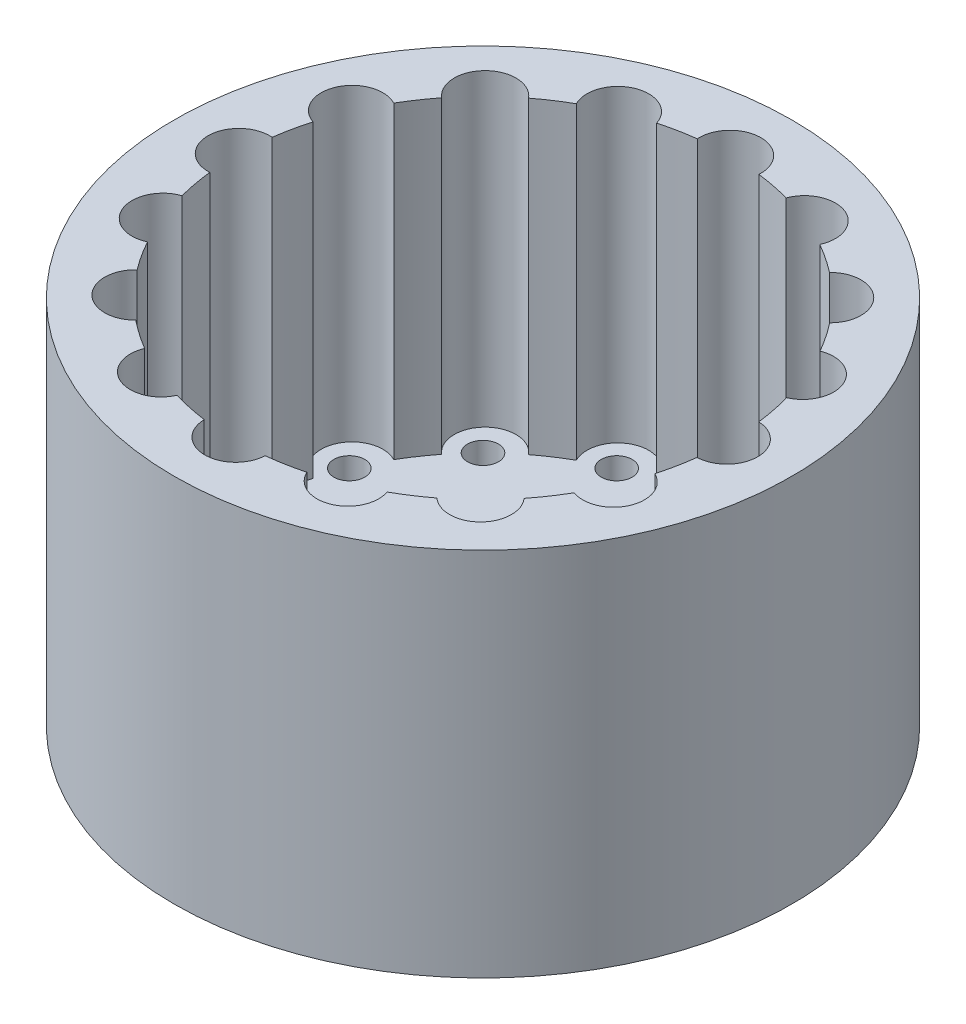
SolidWorks part; units mm, degrees
ref_plane "Front Plane" through (0, 0, 0) normal (0, 0, 1) x (1, 0, 0)
ref_plane "Top Plane" through (0, 0, 0) normal (0, 1, 0) x (1, 0, 0)
ref_plane "Right Plane" through (0, 0, 0) normal (1, 0, 0) x (0, 0, -1)
sketch "Sketch1" plane through (0, 0, 0) normal (0, 1, 0) x (1, 0, 0)
  arc A0 (-38.4721, 10.9498) -> (-39.6225, 5.4827) centre (0, 0) ccw
  arc A1 (4.9902, 39.6875) -> (-4.9902, 39.6875) centre (0, 40) ccw
  arc A2 (19.7423, 34.7885) -> (10.5038, 38.5963) centre (15.1971, 36.8722) ccw
  arc A3 (31.5425, 24.5981) -> (24.4561, 31.6528) centre (28.0405, 28.1668) ccw
  arc A4 (38.5639, 10.6218) -> (34.7247, 19.8543) centre (36.5748, 15.2091) ccw
  arc A5 (39.6831, -5.0248) -> (39.6903, 4.9683) centre (39.5008, -0.0281) ccw
  arc A6 (34.6812, -19.9303) -> (38.5373, -10.718) centre (36.373, -15.2253) ccw
  arc A7 (24.305, -31.769) -> (31.416, -24.7596) centre (27.6676, -28.0686) ccw
  arc A8 (10.1649, -38.6869) -> (19.4331, -34.9622) centre (14.7099, -36.6029) ccw
  arc A9 (-5.5266, -39.6164) -> (4.4678, -39.7497) centre (-0.5273, -39.5289) ccw
  arc A10 (-20.3279, -34.4496) -> (-11.148, -38.4151) centre (-15.7245, -36.4011) ccw
  arc A11 (-31.9737, -24.0351) -> (-25.0145, -31.2134) centre (-28.5678, -27.6957) ccw
  arc A12 (-38.7274, -10.0096) -> (-35.0397, -19.2929) centre (-37.1021, -14.7381) ccw
  arc A13 (-39.6225, 5.4827) -> (-39.7469, -4.4929) centre (-40.0281, 0.4992) ccw
  arc A14 (-34.5711, 20.1207) -> (-38.4721, 10.9498) centre (-36.9003, 15.6963) ccw
  arc A15 (-24.3492, 31.7351) -> (-31.4368, 24.7331) centre (-28.1949, 28.5397) ccw
  arc A16 (-10.477, 38.6035) -> (-19.6974, 34.814) centre (-15.2373, 37.074) ccw
  circle A17 centre (0, 0) radius 50
  arc A18 (-31.4368, 24.7331) -> (-34.5711, 20.1207) centre (0, 0) ccw
  arc A19 (-19.6974, 34.814) -> (-24.3492, 31.7351) centre (0, 0) ccw
  arc A20 (-4.9902, 39.6875) -> (-10.477, 38.6035) centre (0, 0) ccw
  arc A21 (10.5038, 38.5963) -> (4.9902, 39.6875) centre (0, 0) ccw
  arc A22 (24.4561, 31.6528) -> (19.7423, 34.7885) centre (0, 0) ccw
  arc A23 (34.7247, 19.8543) -> (31.5425, 24.5981) centre (0, 0) ccw
  arc A24 (39.6903, 4.9683) -> (38.5639, 10.6218) centre (0, 0) ccw
  arc A25 (38.5373, -10.718) -> (39.6831, -5.0248) centre (0, 0) ccw
  arc A26 (31.416, -24.7596) -> (34.6812, -19.9303) centre (0, 0) ccw
  arc A27 (19.4331, -34.9622) -> (24.305, -31.769) centre (0, 0) ccw
  arc A28 (-11.148, -38.4151) -> (-5.5266, -39.6164) centre (0, 0) ccw
  arc A29 (-25.0145, -31.2134) -> (-20.3279, -34.4496) centre (0, 0) ccw
  arc A30 (-35.0397, -19.2929) -> (-31.9737, -24.0351) centre (0, 0) ccw
  arc A31 (-39.7469, -4.4929) -> (-38.7274, -10.0096) centre (0, 0) ccw
  arc A32 (4.4678, -39.7497) -> (10.1649, -38.6869) centre (0, 0) ccw
  point P2 (0, 0)
  point P3 (0, 0)
  point P31 (-107.6814, 18.7358)
  point P38 (-0.2637, 0.2355)
  point P55 (0, 0)
  point P56 (0, 0)
  dimension "D1" = 16
  dimension "D2" = 100
  dimension "D3" = 5
extrude "Boss-Extrude1" add sketch "Sketch1" along normal blind 50
sketch "Sketch2" plane through (0, 0, 0) normal (0, -1, 0) x (1, 0, 0)
  circle A0 centre (0, 0) radius 50
extrude "Boss-Extrude2" add sketch "Sketch2" along normal blind 10
sketch "Sketch3" plane through (0, 0, 0) normal (0, 1, 0) x (1, 0, 0)
  circle A0 centre (0, 40) radius 2.5
  circle A1 centre (15.3073, 36.9552) radius 2.5
  circle A2 centre (28.2843, 28.2843) radius 2.5
  circle A3 centre (36.9552, 15.3073) radius 2.5
  circle A4 centre (40, 0) radius 2.5
  circle A5 centre (36.9552, -15.3073) radius 2.5
  circle A6 centre (28.2843, -28.2843) radius 2.5
  circle A7 centre (15.3073, -36.9552) radius 2.5
  circle A8 centre (0, -40) radius 2.5
  circle A9 centre (-15.3073, -36.9552) radius 2.5
  circle A10 centre (-28.2843, -28.2843) radius 2.5
  circle A11 centre (-36.9552, -15.3073) radius 2.5
  circle A12 centre (-40, 0) radius 2.5
  circle A13 centre (-36.9552, 15.3073) radius 2.5
  circle A14 centre (-28.2843, 28.2843) radius 2.5
  circle A15 centre (-15.3073, 36.9552) radius 2.5
  point P35 (0, 0)
  dimension "D1" = 5
  dimension "D2" = 16
extrude "Cut-Extrude1" cut sketch "Sketch3" against normal blind 4
